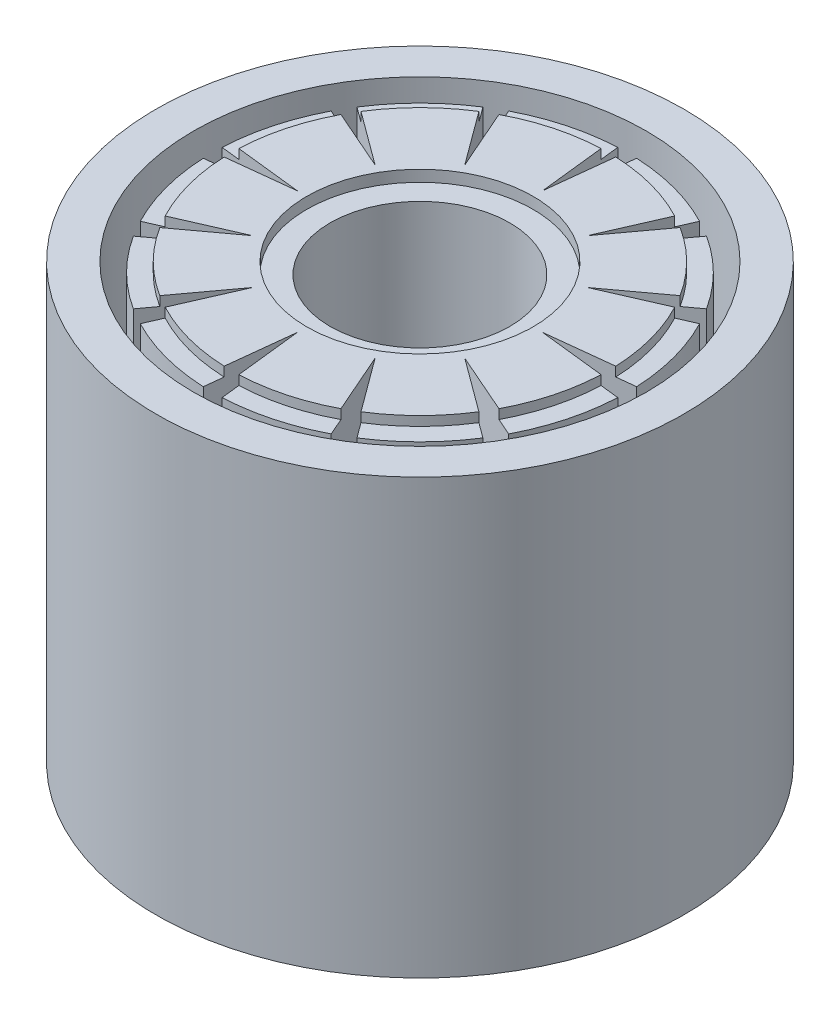
SolidWorks part; units mm, degrees
material "Cast Stainless Steel"
ref_plane "Front Plane" through (0, 0, 0) normal (0, 0, 1) x (1, 0, 0)
ref_plane "Top Plane" through (0, 0, 0) normal (0, 1, 0) x (1, 0, 0)
ref_plane "Right Plane" through (0, 0, 0) normal (1, 0, 0) x (0, 0, -1)
sketch "Sketch2" plane through (0, 0, 0) normal (0, 0, 1) x (1, 0, 0)
  line L0 (0, 0) -> (0, 21.3606) construction
  line L5 (4, 0) -> (12.5, 0)
  line L6 (12.5, 0) -> (14, 4)
  line L7 (14, 4) -> (14, 6)
  line L8 (14, 6) -> (6, 6)
  line L9 (6, 6) -> (6, 7)
  line L10 (6, 7) -> (11, 7)
  line L11 (11, 7) -> (11, 30)
  line L12 (11, 30) -> (4, 30)
  line L13 (4, 30) -> (4, 27)
  line L14 (4, 27) -> (3, 27)
  line L15 (3, 27) -> (3, 3)
  line L16 (3, 3) -> (4, 3)
  line L17 (4, 3) -> (4, 0)
  line L18 (14, 6) -> (14, 23.0761) construction
  line L19 (10, 30) -> (10, 29.5)
  line L20 (10, 29.5) -> (11, 29.5)
  line L21 (10, 7) -> (10, 7.5)
  line L22 (10, 7.5) -> (11, 7.5)
  dimension "D1" = 28
  dimension "D2" = 6
  dimension "D3" = 1.5
  dimension "D4" = 4
  dimension "D5" = 6
  dimension "D6" = 8
  dimension "D7" = 3
  dimension "D8" = 30
  dimension "D9" = 12
  dimension "D10" = 3
  dimension "D11" = 1
  dimension "D12" = 1
  dimension "D13" = 22
revolve "Revolve1" add sketch "Sketch2" angle 360 about L0 region at (7.3683, 14.4403, 0)
sketch "Sketch3" plane through (0, 0, 0) normal (0, 0, 1) x (1, 0, 0)
  line L0 (-11, 7) -> (11, 7) construction
  line L1 (14, 7) -> (12, 7)
  line L2 (14, 7) -> (14, 30)
  line L3 (14, 30) -> (12, 30)
  line L4 (12, 7) -> (12, 30)
  line L5 (11, 30) -> (-11, 30) construction
  line L6 (14, 4) -> (14, 6) construction
  line L7 (0, 0) -> (0, 26.8317) construction
  dimension "D1" = 2
revolve "Revolve2" add sketch "Sketch3" angle 360 about L7
sketch "Sketch4" plane through (0, 0, 0) normal (0, -1, 0) x (1, 0, 0)
  line L0 (0, 9.5) -> (0, -9.5) construction
  line L1 (-8, 0) -> (8, 0) construction
  circle A0 centre (-8, 0) radius 1.25
  circle A1 centre (0, 9.5) radius 1.25
  circle A2 centre (8, 0) radius 1.25
  circle A3 centre (0, -9.5) radius 1.25
  dimension "D3" = 2.5
  dimension "D1" = 16
  dimension "D2" = 19
extrude "Cut-Extrude1" cut sketch "Sketch4" against normal up to next (6 mm away)
sketch "Sketch5" plane through (0, 30, 0) normal (0, 1, 0) x (1, 0, 0)
  line L2 (0, 6.5) -> (-0.5, 10.9886)
  line L3 (0, 6.5) -> (0.5, 10.9886)
  circle A0 centre (0, 0) radius 6 construction
  circle A1 centre (0, 0) radius 6 construction
  circle A2 centre (0, 0) radius 11 construction
  circle A3 centre (0, 0) radius 11 construction
  arc A6 (-0.5, 10.9886) -> (0.5, 10.9886) centre (0, 0) cw
  circle A7 centre (0, 0) radius 6.5 construction
  point P13 (0, 11)
  dimension "D1" = 1
  dimension "D2" = 0.5
extrude "Cut-Extrude2" cut sketch "Sketch5" against normal up to surface (23 mm away) up to face at (0, 7, -10)
pattern_circular "CirPattern1" count 12 over 360 about axis through (0, 30, 0) along (0, -1, 0) of "Cut-Extrude2"
sketch "Sketch6" plane through (0, 30, 0) normal (0, 1, 0) x (1, 0, 0)
  circle A0 centre (0, 0) radius 6
  circle A1 centre (0, 0) radius 4.5
  dimension "D1" = 12
  dimension "D2" = 9
extrude "Cut-Extrude3" cut sketch "Sketch6" against normal blind 0.6
sketch "Sketch7" plane through (0, 0, 0) normal (1, 0, 0) x (0, 0, -1)
  line L0 (0, 0) -> (0, 6)
  line L2 (-6, 7) -> (6, 7) construction
  line L3 (-6, 7) -> (6, 7) construction
  line L4 (0, 0) -> (14, 0)
  line L5 (14, 0) -> (14, 7)
  line L6 (14, 4) -> (14, 6) construction
  line L7 (0, 6) -> (6, 6)
  line L8 (6, 6) -> (6, 7)
  line L9 (6, 7) -> (14, 7)
  line L10 (4.6593, 30) -> (0.389, 30) construction
  dimension "D1" = 24
revolve "Cut-Revolve1" cut sketch "Sketch7" angle 360 about L0
sketch "Sketch8" plane through (0, 6, 0) normal (0, -1, 0) x (1, 0, 0)
  circle A0 centre (0, 0) radius 4.7625
  dimension "D1" = 9.525
extrude "Cut-Extrude4" cut sketch "Sketch8" against normal through all
sketch "Sketch9" plane through (0, 30, 0) normal (0, 1, 0) x (1, 0, 0)
  line L0 (0, -3.9688) -> (0, 3.9688) construction
  circle A0 centre (0, 3.9688) radius 1.5875
  circle A1 centre (0, -3.9688) radius 1.5875
  point P4 (0, 2.3813)
  point P5 (0, -2.3813)
  dimension "D1" = 3.175
  dimension "D2" = 4.7625
extrude "Cut-Extrude5" [suppressed] cut sketch "Sketch9" against normal through all
equation "\"D1@Sketch8\"=.375in"
equation "\"D1@Sketch9\"=.125in"
equation "\"D2@Sketch9\"=.1875in"
